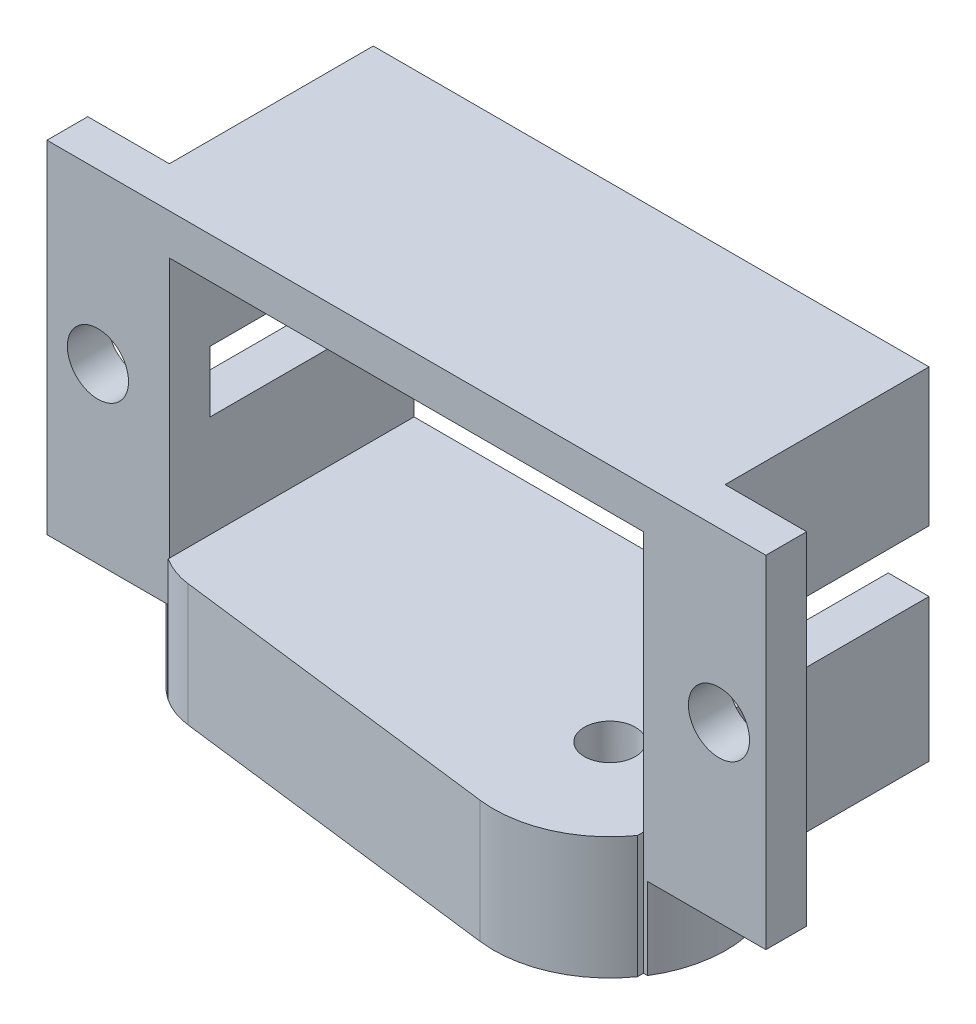
SolidWorks part; units mm, degrees
ref_plane "Front Plane" through (0, 0, 0) normal (0, 0, 1) x (1, 0, 0)
ref_plane "Top Plane" through (0, 0, 0) normal (0, 1, 0) x (1, 0, 0)
ref_plane "Right Plane" through (0, 0, 0) normal (1, 0, 0) x (0, 0, -1)
sketch "Sketch1" plane through (0, 0, 0) normal (0, 0, 1) x (1, 0, 0)
  line L0 (-2, 2) -> (25.25, 2)
  line L1 (0, 0) -> (23.25, 0)
  line L2 (0, 0) -> (0, -12.75)
  line L3 (0, -12.75) -> (23.25, -12.75)
  line L4 (23.25, 0) -> (23.25, -12.75)
  line L5 (25.25, 2) -> (25.25, -14.75)
  line L6 (-2, -14.75) -> (25.25, -14.75)
  line L7 (-2, 2) -> (-2, -14.75)
  dimension "D1" = 12.75
  dimension "D2" = 23.25
  dimension "D3" = 2
extrude "Boss-Extrude1" add sketch "Sketch1" along normal blind 18
sketch "Sketch3" plane through (0, 0, 0) normal (0, 0, -1) x (-1, 0, 0)
  line L1 (-23.25, 0) -> (0, 0)
  line L2 (-23.25, 0) -> (-23.25, -12.75)
  line L3 (-23.25, -12.75) -> (0, -12.75)
  line L4 (0, 0) -> (0, -12.75)
extrude "Boss-Extrude2" add sketch "Sketch3" against normal blind 2
sketch "Sketch7" plane through (-2, 0, 0) normal (-1, 0, 0) x (0, 0, 1)
  line L0 (18, 2) -> (0, 2) construction
  line L1 (2, -4) -> (4, -4)
  line L2 (2, -4) -> (2, -9)
  line L3 (2, -9) -> (4, -9)
  line L4 (4, -4) -> (4, -9)
  line L6 (0, 2) -> (0, -14.75) construction
  dimension "D1" = 6
  dimension "D2" = 5
  dimension "D3" = 2
  dimension "D4" = 2
extrude "Cut-Extrude1" cut sketch "Sketch7" against normal blind 2
sketch "Sketch10" plane through (0, 0, 18) normal (0, 0, 1) x (1, 0, 0)
  line L1 (-2, 2) -> (25.25, 2)
  line L2 (-2, 2) -> (-2, -14.75)
  line L3 (-2, -14.75) -> (25.25, -14.75)
  line L4 (25.25, 2) -> (25.25, -14.75)
  line L5 (0, 0) -> (23.25, 0)
  line L6 (0, 0) -> (0, -12.75)
  line L7 (0, -12.75) -> (23.25, -12.75)
  line L8 (23.25, 0) -> (23.25, -12.75)
  line L10 (-2, -0.0396) -> (-2, -13.0396)
  line L13 (-2, 2) -> (-9, 2)
  line L14 (-2, 2) -> (-2, -14.75)
  line L15 (-2, -14.75) -> (-9, -14.75)
  line L16 (-9, 2) -> (-9, -14.75)
  line L17 (25.25, 2) -> (32.25, 2)
  line L18 (25.25, 2) -> (25.25, -14.75)
  line L19 (25.25, -14.75) -> (32.25, -14.75)
  line L20 (32.25, 2) -> (32.25, -14.75)
  line M7 (-2, 2) -> (-2, -14.75)
  line M8 (-2, -14.75) -> (25.25, -14.75)
  line M9 (25.25, -14.75) -> (25.25, 2)
  line M10 (25.25, 2) -> (-2, 2)
  line M11 (23.25, -12.75) -> (0, -12.75)
  line M12 (0, -12.75) -> (0, 0)
  line M13 (0, 0) -> (23.25, 0)
  line M14 (23.25, 0) -> (23.25, -12.75)
  dimension "D1" = 7
  dimension "D2" = 7
extrude "Boss-Extrude3" add sketch "Sketch10" along normal blind 2 contours L13 L16 L15 L2 M7 | L2 M10 M7 M8 M9 M14 M11 M12 M13 | L20 L17 L19 M9 region at (11.625, 1.6801, 18) region at (-5.5, -6.375, 18) region at (28.75, -6.375, 18)
sketch "Sketch11" plane through (0, 0, 18) normal (0, 0, -1) x (-1, 0, 0)
  line L0 (2, 2) -> (9, 2) construction
  line L1 (6, 2) -> (3, 2)
  line L3 (6, -14.75) -> (3, -14.75)
  line L5 (2, -14.75) -> (9, -14.75) construction
  line L7 (2, 2) -> (2, -14.75) construction
  circle A0 centre (3.5, -6.25) radius 1.5
  dimension "D1" = 8.5
  dimension "D2" = 1.5
extrude "Cut-Extrude3" cut sketch "Sketch11" against normal blind 2 contours A0 | A0 | A0 | A0 region at (-3.5, -6.25, 18)
sketch "Sketch12" plane through (0, 0, 18) normal (0, 0, -1) x (-1, 0, 0)
  line L0 (-32.25, 2) -> (-25.25, 2) construction
  line L1 (-31, 2) -> (-28, 2)
  line L3 (-31, -14.75) -> (-28, -14.75)
  line L5 (-32.25, -14.75) -> (-25.25, -14.75) construction
  line L7 (-25.25, -14.75) -> (-25.25, 2) construction
  circle A0 centre (-26.95, -6.25) radius 1.5
  dimension "D1" = 8.5
  dimension "D2" = 1.7
extrude "Cut-Extrude4" cut sketch "Sketch12" against normal blind 2 contours A0 | A0 | A0 | A0 region at (26.95, -6.25, 18)
fillet "Fillet11" radius 1 6 edges at (0, -9, 3) (0, -4, 3) (0, -6.5, 4) (-2, -6.5, 4) (-2, -4, 3) (-2, -9, 3)
sketch "Sketch13" plane through (0, 0, 18) normal (0, 0, -1) x (-1, 0, 0)
  line L0 (-32.25, -14.75) -> (-25.25, -14.75) construction
  line L1 (-32.25, 2) -> (-29.25, 2)
  line L2 (-32.25, 2) -> (-32.25, -14.75)
  line L3 (-32.25, -14.75) -> (-29.25, -14.75)
  line L4 (-29.25, 2) -> (-29.25, -14.75)
  line L5 (2, -14.75) -> (9, -14.75) construction
  line L6 (9, 2) -> (6, 2)
  line L7 (9, 2) -> (9, -14.75)
  line L8 (9, -14.75) -> (6, -14.75)
  line L9 (6, 2) -> (6, -14.75)
  dimension "D1" = 3
  dimension "D2" = 3
extrude "Cut-Extrude5" cut sketch "Sketch13" against normal blind 10
sketch "Sketch14" plane through (0, 2, 0) normal (0, 1, 0) x (1, 0, 0)
  line L0 (25.25, -18) -> (25.25, 0) construction
  line L1 (-2, 0) -> (25.25, 0)
  line L2 (-2, 0) -> (-2, -8)
  line L3 (-2, -8) -> (25.25, -8)
  line L4 (25.25, 0) -> (25.25, -8)
  line L5 (-2, -18) -> (-6, -18) construction
  dimension "D1" = 10
extrude "Cut-Extrude6" cut sketch "Sketch14" against normal up to surface (16.75 mm away) up to face at (11.625, -14.75, 14)
sketch "Sketch16" plane through (0, 0, 20) normal (0, 0, 1) x (1, 0, 0)
  line L5 (0, -12.75) -> (0, -14.75)
  line L6 (29.25, -14.75) -> (-6, -14.75) construction
  line L7 (0, -14.75) -> (23.25, -14.75)
  line L8 (23.25, -14.75) -> (23.25, -12.75)
  line L10 (0, -12.75) -> (23.25, -12.75)
  line L14 (23.25, -12.75) -> (23.25, 0)
  line L15 (0, -12.75) -> (23.25, -12.75)
  line L16 (0, 0) -> (0, -12.75)
  line L17 (23.25, 0) -> (0, 0)
  line L18 (23.25, -12.75) -> (23.25, 0)
  line L20 (0, 0) -> (0, -12.75)
  line L21 (23.25, 0) -> (0, 0)
  line M4 (-6, -14.75) -> (29.25, -14.75)
  line M8 (23.25, -12.75) -> (0, -12.75)
  dimension "D1" = 0
extrude "Boss-Extrude5" add sketch "Sketch16" along normal blind 7.6 contours L8 L5 M4 M8 region at (11.625, -13.75, 20)
sketch "Sketch19" plane through (0, 0, 8) normal (0, 0, -1) x (-1, 0, 0)
  line L0 (-26.95, -4.75) -> (-23.25, -4.75)
  line L1 (-23.25, -12.75) -> (-23.25, 0) construction
  line L2 (-23.25, -4.75) -> (-23.25, -7.75)
  line L3 (-23.25, -7.75) -> (-25.25, -7.75)
  line L4 (-25.25, -14.75) -> (-25.25, 2) construction
  line L5 (-25.25, -7.75) -> (-25.25, -4.75)
  line L6 (-25.25, -14.75) -> (-25.25, 2) construction
  line L7 (3.5, -4.75) -> (0, -4.75)
  line L8 (0, 0) -> (0, -12.75) construction
  line L9 (0, -4.75) -> (0, -7.75)
  line L10 (0, -7.75) -> (2, -7.75)
  line L11 (2, -6.25) -> (2, -14.75) construction
  line L12 (2, -7.75) -> (2, -4.75)
  line L13 (2, 2) -> (2, -6.25) construction
  line L14 (-25.25, -4.75) -> (-23.25, -4.75)
  line L15 (-23.25, -7.75) -> (-25.25, -7.75)
  line L16 (0, -4.75) -> (2, -4.75)
  line L17 (2, -7.75) -> (0, -7.75)
  circle A0 centre (-26.95, -6.25) radius 1.5 construction
  circle A1 centre (3.5, -6.25) radius 1.5 construction
  line M1 (0, 0) -> (0, -12.75)
  line M3 (-23.25, -12.75) -> (-23.25, 0)
  line M6 (2, -14.75) -> (2, 2)
  line M8 (-25.25, 2) -> (-25.25, -14.75)
extrude "Cut-Extrude8" cut sketch "Sketch19" against normal up to surface (10 mm away) contours L10 L7 M1 M6 | L3 L0 M3 M8 region at (24.25, -6.25, 8) region at (-1, -6.25, 8) up to face at (25.45, -6.25, 18)
sketch "Sketch20" plane through (0, -14.75, 0) normal (0, -1, 0) x (1, 0, 0)
  line L0 (2, 17) -> (18.6, 17)
  line L1 (25.25, 8) -> (-2, 8) construction
  line L2 (-2, 18) -> (-2, 8) construction
  line L3 (1.3222, 20.5938) -> (20.8547, 23.0246)
  line L4 (1.5074, 19.1053) -> (21.0399, 21.536)
  line L5 (1.0027, 14.9575) -> (19.59, 12.6444)
  line L6 (0.8174, 13.469) -> (19.4048, 11.1559)
  circle A0 centre (18.6, 17) radius 4.2
  circle A1 centre (2, 17) radius 2.15
  circle A2 centre (2, 17) radius 3.65
  circle A3 centre (18.6, 17) radius 5.7
  line M9 (29.25, 20) -> (23.25, 20)
  line M10 (23.25, 20) -> (23.25, 27.6)
  line M12 (0, 27.6) -> (0, 20)
  line M13 (0, 20) -> (-6, 20)
  dimension "D1" = 8.4
  dimension "D2" = 4.3
  dimension "D3" = 16.6
  dimension "D4" = 9
  dimension "D5" = 4
  dimension "D6" = 1.5
  dimension "D7" = 1.5
extrude "Boss-Extrude6" add sketch "Sketch20" along normal blind 4 contours L4 A2 L5 A1 M12 M13 | A3 L3 A2 L4 | A3 L4 A0 L5 M10 M9 | A3 L5 A2 L6 region at (-0.2465, -14.75, 17) region at (9.5346, -14.75, 20.9168) region at (9.5346, -14.75, 13.0832) region at (15.9644, -14.75, 21.8821)
sketch "Sketch21" plane through (0, -14.75, 0) normal (0, -1, 0) x (1, 0, 0)
  circle A0 centre (18.6, 17) radius 1.25
  dimension "D1" = 2.5
extrude "Cut-Extrude9" cut sketch "Sketch21" against normal up to surface (2 mm away) up to face at (11.625, -12.75, 18.5333)
sketch "Sketch23" plane through (0, -14.75, 0) normal (0, -1, 0) x (1, 0, 0)
  line L0 (11.1, 21.1007) -> (0.4062, 19.9989)
  line L1 (0.4062, 19.9989) -> (-0.9545, 17.32)
  line L2 (-0.9545, 17.32) -> (0.3877, 14.426)
  line L3 (0.3877, 14.426) -> (11.1, 12.8678)
  line L4 (11.1, 12.8678) -> (11.1, 21.1007)
  circle A0 centre (18.6, 17) radius 1.25 construction
  dimension "D1" = 7.5
extrude "Boss-Extrude7" add sketch "Sketch23" along normal blind 1
sketch "Sketch24" plane through (0, -14.75, 0) normal (0, -1, 0) x (1, 0, 0)
  line L0 (0.8326, 20.5329) -> (21.7275, 23.1332)
  line L1 (0, 20) -> (0, 27.6)
  line L2 (0, 27.6) -> (23.25, 27.6)
  line L3 (23.25, 27.6) -> (23.25, 20)
  circle A0 centre (2, 17) radius 3.65
  circle A1 centre (18.6, 17) radius 5.7
  arc M2 (17.8961, 22.6564) -> (23.25, 20.2966) centre (18.6, 17) cw
  line M3 (23.25, 20.2966) -> (23.25, 27.6)
  line M4 (23.25, 27.6) -> (0, 27.6)
  line M5 (0, 27.6) -> (0, 20.0533)
  arc M6 (0, 20.0533) -> (1.5492, 20.6221) centre (2, 17) cw
  line M7 (1.5492, 20.6221) -> (17.8961, 22.6564)
  dimension "D1" = 7.3
  dimension "D2" = 11.4
extrude "Cut-Extrude11" cut sketch "Sketch24" against normal blind 12 contours M7 M2 M3 M4 M5 M6 region at (11.0332, -14.75, 24.5869)
